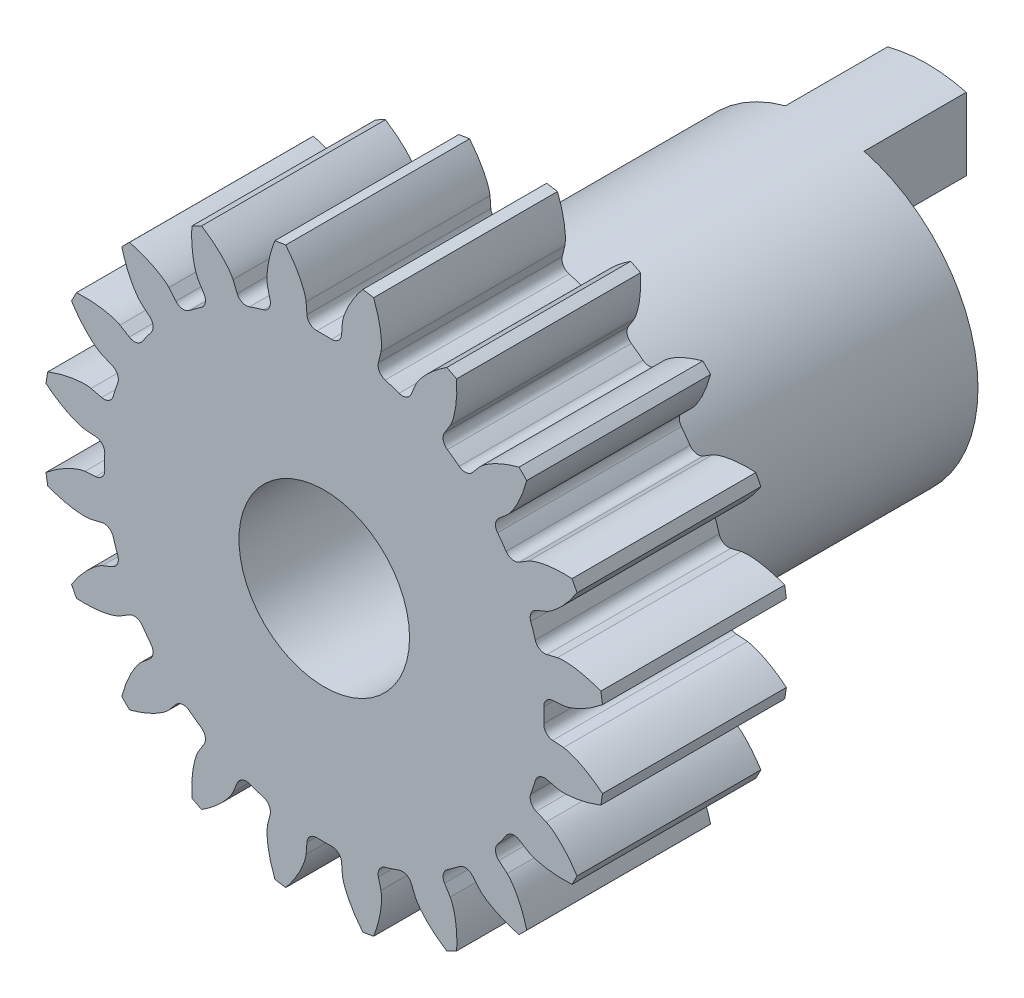
SolidWorks part; units mm, degrees
ref_plane "Front Plane" through (0, 0, 0) normal (0, 0, 1) x (1, 0, 0)
ref_plane "Top Plane" through (0, 0, 0) normal (0, 1, 0) x (1, 0, 0)
ref_plane "Right Plane" through (0, 0, 0) normal (1, 0, 0) x (0, 0, -1)
ref_axis "Gear Axis" through (0, 0, -43.7625) along (0, 0, 1)
sketch "Blank Sketch" plane through (0, 0, 0) normal (0, 0, 1) x (1, 0, 0)
  circle A0 centre (0, 0) radius 13.75
  dimension "OD" = 27.5
extrude "Blank" add sketch "Blank Sketch" along normal blind 9
sketch "Tooth Space Sketch" plane through (0, 0, 0) normal (0, 0, 1) x (1, 0, 0)
  line L0 (11.7126, 0.8876) -> (11.1829, 0.8474)
  line L1 (11.7126, -0.8876) -> (11.1829, -0.8474)
  line L2 (14.705, 2.9601) -> (14.705, -2.9601)
  arc A0 (11.1829, 0.8474) -> (10.744, 0.358) centre (11.2188, 0.3738) ccw
  arc A1 (10.744, -0.358) -> (11.1829, -0.8474) centre (11.2188, -0.3738) ccw
  arc A2 (10.744, -0.358) -> (10.744, 0.358) centre (0, 0) ccw
  spline S0 degree 4 poles (11.7126, 0.8876) (11.718, 0.8881) (11.7333, 0.8898) (11.7621, 0.8941) (11.8087, 0.9028) (11.8679, 0.9161) (11.9438, 0.936) (12.0325, 0.9629) (12.1291, 0.9959) (12.2333, 1.0356) (12.3362, 1.0785) (12.4379, 1.1244) (12.5383, 1.1729) (12.6587, 1.2348) (12.8015, 1.3135) (12.9658, 1.4118) (13.1489, 1.5308) (13.3319, 1.66) (13.5089, 1.7935) (13.6838, 1.9356) (13.8504, 2.0781) (14.0193, 2.2333) (14.173, 2.3803) (14.3404, 2.5526) (14.474, 2.694) (14.6449, 2.8885) (14.7442, 3.0057) (14.8584, 3.1456) (14.9081, 3.2092) (14.9387, 3.2482) knots 0 0 0 0 0 0.005377 0.015084 0.028532 0.04661 0.064855 0.092111 0.119476 0.146842 0.174209 0.201575 0.228941 0.256307 0.307035 0.361767 0.4165 0.471232 0.525964 0.580697 0.635429 0.690161 0.744894 0.799626 0.854358 0.909091 0.954545 1 1 1 1 1 construction
  spline S1 degree 4 poles (11.7126, 0.8876) (11.718, 0.8881) (11.7333, 0.8898) (11.7621, 0.8941) (11.8087, 0.9028) (11.8679, 0.9161) (11.9438, 0.936) (12.0325, 0.9629) (12.1291, 0.9959) (12.2333, 1.0356) (12.3362, 1.0785) (12.4379, 1.1244) (12.5383, 1.1729) (12.6587, 1.2348) (12.8015, 1.3135) (12.9658, 1.4118) (13.1489, 1.5308) (13.3319, 1.66) (13.5089, 1.7935) (13.6838, 1.9356) (13.8504, 2.0781) (14.0193, 2.2333) (14.173, 2.3803) (14.3404, 2.5526) (14.474, 2.694) (14.6078, 2.8463) (14.6723, 2.9214) (14.705, 2.9601) knots 0 0 0 0 0 0.005377 0.015084 0.028532 0.04661 0.064855 0.092111 0.119476 0.146842 0.174209 0.201575 0.228941 0.256307 0.307035 0.361767 0.4165 0.471232 0.525964 0.580697 0.635429 0.690161 0.744894 0.799626 0.854358 0.909091 0.909091 0.909091 0.909091 0.909091
  spline S2 degree 4 poles (11.7126, -0.8876) (11.718, -0.8881) (11.7333, -0.8898) (11.7621, -0.8941) (11.8087, -0.9028) (11.8679, -0.9161) (11.9438, -0.936) (12.0325, -0.9629) (12.1291, -0.9959) (12.2333, -1.0356) (12.3362, -1.0785) (12.4379, -1.1244) (12.5383, -1.1729) (12.6587, -1.2348) (12.8015, -1.3135) (12.9658, -1.4118) (13.1489, -1.5308) (13.3319, -1.66) (13.5089, -1.7935) (13.6838, -1.9356) (13.8504, -2.0781) (14.0193, -2.2333) (14.173, -2.3803) (14.3404, -2.5526) (14.474, -2.694) (14.6449, -2.8885) (14.7442, -3.0057) (14.8584, -3.1456) (14.9081, -3.2092) (14.9387, -3.2482) knots 0 0 0 0 0 0.005377 0.015084 0.028532 0.04661 0.064855 0.092111 0.119476 0.146842 0.174209 0.201575 0.228941 0.256307 0.307035 0.361767 0.4165 0.471232 0.525964 0.580697 0.635429 0.690161 0.744894 0.799626 0.854358 0.909091 0.954545 1 1 1 1 1 construction
  spline S3 degree 4 poles (11.7126, -0.8876) (11.718, -0.8881) (11.7333, -0.8898) (11.7621, -0.8941) (11.8087, -0.9028) (11.8679, -0.9161) (11.9438, -0.936) (12.0325, -0.9629) (12.1291, -0.9959) (12.2333, -1.0356) (12.3362, -1.0785) (12.4379, -1.1244) (12.5383, -1.1729) (12.6587, -1.2348) (12.8015, -1.3135) (12.9658, -1.4118) (13.1489, -1.5308) (13.3319, -1.66) (13.5089, -1.7935) (13.6838, -1.9356) (13.8504, -2.0781) (14.0193, -2.2333) (14.173, -2.3803) (14.3404, -2.5526) (14.474, -2.694) (14.6078, -2.8463) (14.6723, -2.9214) (14.705, -2.9601) knots 0 0 0 0 0 0.005377 0.015084 0.028532 0.04661 0.064855 0.092111 0.119476 0.146842 0.174209 0.201575 0.228941 0.256307 0.307035 0.361767 0.4165 0.471232 0.525964 0.580697 0.635429 0.690161 0.744894 0.799626 0.854358 0.909091 0.909091 0.909091 0.909091 0.909091
  dimension "Root" = 10.75
  dimension "Fillet" = 0.475
extrude "Tooth Space" cut sketch "Tooth Space Sketch" against normal through all both and the other way through all both
pattern_circular "Teeth" count 20 over 360 about axis through (0, 0, -43.7625) along (0, 0, 1) of "Tooth Space"
sketch "Bore Sketch" plane through (0, 0, 0) normal (0, 0, 1) x (1, 0, 0)
  circle A0 centre (0, 0) radius 4.175
  dimension "Bore" = 8.35
extrude "Bore" cut sketch "Bore Sketch" against normal through all both and the other way through all both
sketch "Sketch1" plane through (0, 0, 9) normal (0, 0, 1) x (1, 0, 0)
  circle A0 centre (0, 0) radius 4.175 construction
  circle A1 centre (0, 0) radius 4.175
  circle A4 centre (0, 0) radius 7.5
  dimension "D1" = 15
extrude "Boss-Extrude1" add sketch "Sketch1" against normal blind 50.25
ref_plane "Plane1" through (0, 0, -20.5) normal (0, 0, 1) x (1, 0, 0)
split "Split1" trim tools "Plane1" bodies to split 105 resulting bodies 108
sketch "Sketch2" plane through (0, 0, -20.5) normal (0, 0, -1) x (-1, 0, 0)
  line L0 (-1.925, 7.2487) -> (-1.925, -7.2487)
  line L1 (1.925, 7.2487) -> (1.925, -7.2487)
  circle A0 centre (0, 0) radius 7.5 construction
  arc A1 (-1.925, 7.2487) -> (-1.925, -7.2487) centre (0, 0) ccw
  arc A2 (1.925, 7.2487) -> (-1.925, 7.2487) centre (0, 0) ccw construction
  arc A3 (-1.925, -7.2487) -> (1.925, -7.2487) centre (0, 0) ccw construction
  arc A4 (1.925, -7.2487) -> (1.925, 7.2487) centre (0, 0) ccw
  dimension "D1" = 1.925
  dimension "D2" = 1.925
extrude "Cut-Extrude1" cut sketch "Sketch2" against normal blind 5
equation "\"No. of Teeth\"= 20"
equation "\"Module\"= 1.25"
equation "\"Bore Diameter\"= 8.35"
equation "\"Pressure Angle\"= 20"
equation "\"Outer Diameter\"= ( \"No. of Teeth\" + 2 ) * \"Module\""
equation "\"Pitch Diameter\"= \"No. of Teeth\" * \"Module\""
equation "\"Backlash\"= IIF ( \"Module\" <= 1 , 0.3 * \"Module\" , 0.3 )"
equation "\"Arc Length\"= ( ( \"Module\" * pi ) / 2 + \"Backlash\" )"
equation "\"Fillet Radius\"= 0.38 * \"Module\""
equation "\"Tooth Depth\"= IIF ( \"Module\" <= 1.25 , \"Module\" * 2.4 , \"Module\" * 2.25 )"
equation "\"Face Width\"= 9"
equation "\"Root Diameter\"= \"Outer Diameter\" - 2 * \"Tooth Depth\""
equation "\"Base Diameter\"= \"Pitch Diameter\" * cos ( \"Pressure Angle\" )"
equation "\"Base Radius\"= \"Base Diameter\" / 2"
equation "\"Tooth Thickness\"= \"Module\" * pi - \"Arc Length\""
equation "\"Half Space Angle\"= ( \"Arc Length\" / \"Pitch Diameter\" ) * 180 / pi"
equation "\"Involute Fn\"= tan ( \"Pressure Angle\" ) - \"Pressure Angle\" * pi / 180"
equation "\"Flank Offset\"= \"Arc Length\" / \"Pitch Diameter\" - \"Involute Fn\""
equation "\"Tip Cap Diameter\"= \"Outer Diameter\" + 2 * \"Module\""
equation "\"Flank Start Diameter\"= IIF ( \"Base Diameter\" >= ( \"Root Diameter\" + 3 * \"Fillet Radius\" ) , \"Base Diameter\" , \"Root Diameter\" + 3 * \"Fillet Radius\" )"
equation "\"Involute t1\"= ( abs ( ( \"Flank Start Diameter\" / \"Base Diameter\" ) ^ 2 - 1 ) ) ^ 0.5"
equation "\"Involute t2\"= ( abs ( ( \"Tip Cap Diameter\" / \"Base Diameter\" ) ^ 2 - 1 ) ) ^ 0.5"
equation "\"Flank Arc Radius\"= ( \"Pitch Diameter\" / 2 ) * sin ( \"Pressure Angle\" )"
equation "\"Flank Centre Angle\"= \"Half Space Angle\" + \"Pressure Angle\""
equation "\"OD@Blank Sketch\"= \"Outer Diameter\""
equation "\"Width@Blank\"= \"Face Width\""
equation "\"Root@Tooth Space Sketch\"= \"Root Diameter\" / 2"
equation "\"Fillet@Tooth Space Sketch\"= \"Fillet Radius\""
equation "\"Count@Teeth\"= \"No. of Teeth\""
equation "\"Bore@Bore Sketch\"= \"Bore Diameter\""
